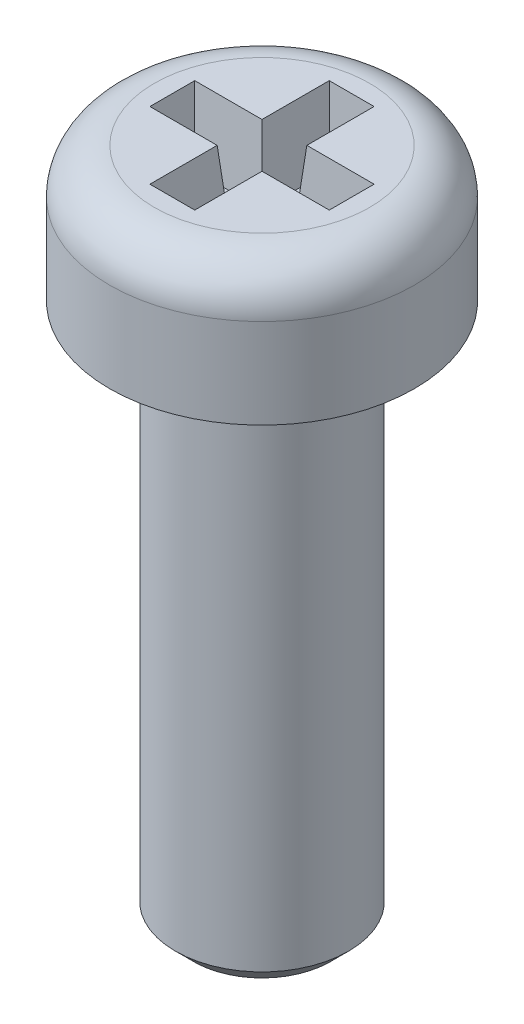
SolidWorks part; units mm, degrees
ref_plane "Front Plane" through (0, 0, 0) normal (0, 0, 1) x (1, 0, 0)
ref_plane "Top Plane" through (0, 0, 0) normal (0, 1, 0) x (1, 0, 0)
ref_plane "Right Plane" through (0, 0, 0) normal (1, 0, 0) x (0, 0, -1)
sketch "Sketch1" plane through (0, 0, 0) normal (0, 1, 0) x (1, 0, 0)
  circle A0 centre (0, 0) radius 1.7
  dimension "D1" = 3.4
extrude "Boss-Extrude1" add sketch "Sketch1" along normal blind 1.5
sketch "Sketch2" plane through (0, 0, 0) normal (0, -1, 0) x (1, 0, 0)
  circle A0 centre (0, 0) radius 0.965
  dimension "D1" = 1.93
extrude "Boss-Extrude2" add sketch "Sketch2" along normal blind 6
chamfer "Chamfer1" distance 0.2 angle 45 1 edges at (0, -6, -0.965)
sketch "Sketch3" plane through (0, 1.5, 0) normal (0, 1, 0) x (1, 0, 0)
  line L0 (0, -1) -> (0, 1)
  line L1 (-1, 0) -> (1, 0)
  point P4 (0, 0)
  point P8 (0, 0)
  dimension "D1" = 2
extrude "Cut-Extrude-Thin1" cut sketch "Sketch3" against normal blind 0.8 draft 5 thin thin type mid plane wall 0.5
fillet "Fillet1" radius 0.5 1 edges at (0, 1.5, 1.7)
ref_axis "Axis1" through (0, -5.8, 0) along (0, 1, 0)
